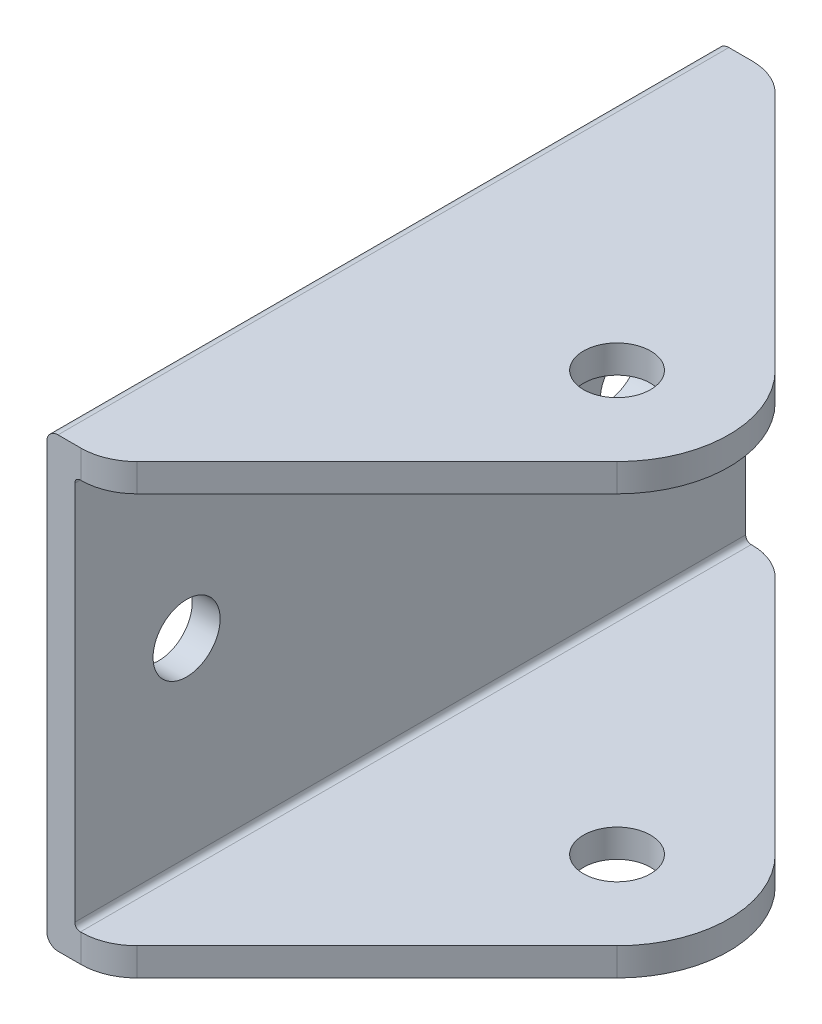
SolidWorks part; units mm, degrees
ref_plane "Спереди" through (0, 0, 0) normal (0, 0, 1) x (1, 0, 0)
ref_plane "Сверху" through (0, 0, 0) normal (0, 1, 0) x (1, 0, 0)
ref_plane "Справа" through (0, 0, 0) normal (1, 0, 0) x (0, 0, -1)
sketch "Эскиз1" plane through (0, 0, 0) normal (0, 0, 1) x (1, 0, 0)
  line L0 (2.5, 2.5) -> (2.5, 37.5)
  line L1 (0, 0) -> (40, 0)
  line L2 (0, 0) -> (0, 40)
  line L3 (0, 40) -> (40, 40)
  line L4 (40, 0) -> (40, 40)
  line L5 (2.5, 37.5) -> (37.5, 37.5)
  line L6 (37.5, 2.5) -> (37.5, 37.5)
  line L7 (2.5, 2.5) -> (37.5, 2.5)
  dimension "D2" = 40
  dimension "D3" = 35
  dimension "D1" = 2.5
extrude "Бобышка-Вытянуть1" add sketch "Эскиз1" along normal blind 100
fillet "Скругление1" radius 1 4 edges at (0, 0, 50) (0, 40, 50) (40, 0, 50) (40, 40, 50)
fillet "Скругление2" radius 0.5 4 edges at (2.5, 2.5, 50) (2.5, 37.5, 50) (37.5, 37.5, 50) (37.5, 2.5, 50)
sketch "Эскиз2" plane through (0, 40, 0) normal (0, 1, 0) x (1, 0, 0)
  line L0 (1, -50) -> (31, -50) construction
  line L1 (1, 0) -> (1, -100) construction
  line L3 (-2.3278, -20) -> (3.0711, -20)
  line L4 (6.6066, -21.4645) -> (28.0711, -42.9289)
  line L5 (-2.3278, -20) -> (-2.3278, -80)
  line L6 (0, -100) -> (0, 0) construction
  line L7 (-2.3278, -80) -> (3.0711, -80)
  line L8 (6.6066, -78.5355) -> (28.0711, -57.0711)
  circle A0 centre (21, -50) radius 3
  circle A1 centre (21, -50) radius 10 construction
  arc A2 (28.0711, -57.0711) -> (28.0711, -42.9289) centre (21, -50) ccw
  arc A3 (3.0711, -20) -> (6.6066, -21.4645) centre (3.0711, -25) cw
  arc A4 (3.0711, -80) -> (6.6066, -78.5355) centre (3.0711, -75) ccw
  point P12 (31, -50)
  point P24 (-2.3278, -50)
  dimension "D1" = 6
  dimension "D2" = 20
  dimension "D6" = 5
  dimension "D3" = 30
  dimension "D4" = 2.3278
  dimension "D5" = 45
  dimension "D7" = 30
extrude "Вырез-Вытянуть1" cut sketch "Эскиз2" against normal blind 100 flip side to cut
sketch "Эскиз3" plane through (2.5, 0, 0) normal (1, 0, 0) x (0, 0, -1)
  line L0 (-80, 20) -> (-20, 20) construction
  line L1 (-80, 37) -> (-80, 3) construction
  line L2 (-20, 3) -> (-20, 37) construction
  line L3 (-50, 37) -> (-50, 3) construction
  line L4 (-20, 37) -> (-80, 37) construction
  line L5 (-80, 3) -> (-20, 3) construction
  circle A0 centre (-70, 20) radius 3
  circle A1 centre (-30, 20) radius 3
  dimension "D1" = 6
  dimension "D2" = 10
extrude "Вырез-Вытянуть2" cut sketch "Эскиз3" against normal blind 100
